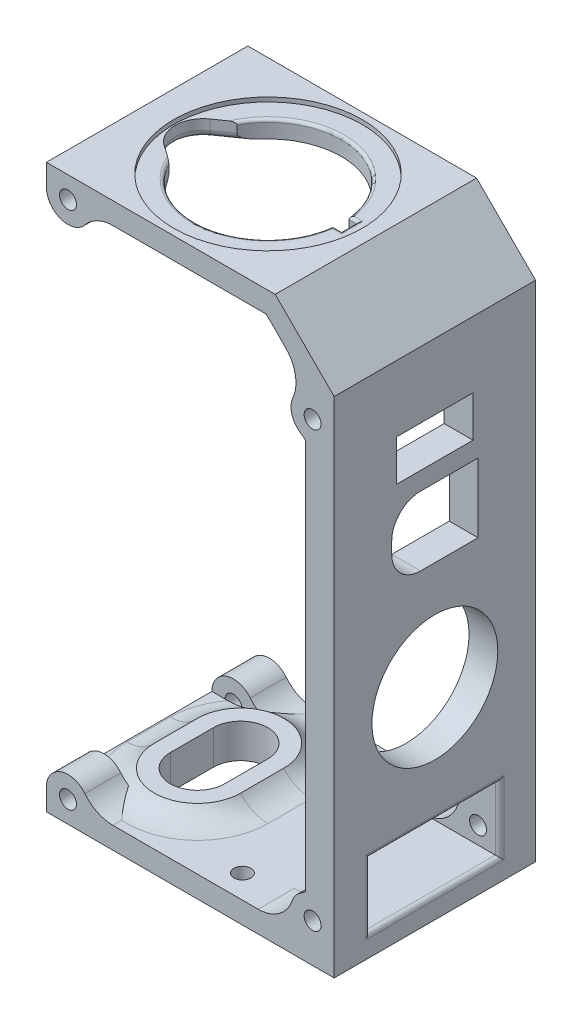
SolidWorks part; units mm, degrees
ref_plane "Front Plane" through (0, 0, 0) normal (0, 0, 1) x (1, 0, 0)
ref_plane "Top Plane" through (0, 0, 0) normal (0, 1, 0) x (1, 0, 0)
ref_plane "Right Plane" through (0, 0, 0) normal (1, 0, 0) x (0, 0, -1)
sketch "Sketch1" plane through (0, 0, 0) normal (0, 0, 1) x (1, 0, 0)
  line L0 (31.8, 78.2) -> (40, 70)
  line L1 (0, 0) -> (40, 0)
  line L3 (0, 78.2) -> (31.8, 78.2)
  line L4 (40, 0) -> (40, 70)
  line L5 (0, 0) -> (0, 3)
  line L6 (6, 75.2) -> (30.5574, 75.2)
  line L7 (35.2, 3) -> (6, 3)
  line L8 (37, 8.4) -> (37, 62.7574)
  line L10 (-74.4457, 75.2) -> (30.5574, 75.2) construction
  line L11 (1.2019, 3) -> (-74.4457, 75.2) construction
  line L12 (30.5574, 75.2) -> (37, 68.7574)
  line L13 (30.5574, 75.2) -> (37, 68.7574) construction
  line L14 (1.2019, 3) -> (37, 3) construction
  line L15 (37, 3) -> (37, 68.7574) construction
  line L16 (0, 78.2) -> (0, 75.2)
  line L17 (-81.934, 78.2) -> (31.8, 78.2) construction
  line L18 (40, 0) -> (40, 70) construction
  line L19 (0, 0) -> (-81.934, 78.2) construction
  arc A0 (37, 68.7574) -> (37, 62.7574) centre (37, 65.7574) ccw
  circle A1 centre (37, 65.7574) radius 1.175
  arc A2 (37, 8.4) -> (35.2, 3) centre (37, 5.4) ccw
  circle A3 centre (37, 5.4) radius 1.175
  arc A4 (6, 3) -> (0, 3) centre (3, 3) ccw
  circle A5 centre (3, 3) radius 1.175
  arc A6 (0, 75.2) -> (6, 75.2) centre (3, 75.2) ccw
  circle A7 centre (3, 75.2) radius 1.175
  dimension "D6" = 6
  dimension "D7" = 2.35
  dimension "D1" = 40
  dimension "D2" = 135
  dimension "D3" = 3
  dimension "D4" = 70
  dimension "D5" = 3
extrude "Boss-Extrude1" add sketch "Sketch1" along normal blind 28
sketch "Sketch2" plane through (0, 78.2, 0) normal (0, 1, 0) x (1, 0, 0)
  line L0 (31.8, -14) -> (-12.3888, -14) construction
  line L1 (31.8, -28) -> (31.8, 0) construction
  circle A0 centre (16.8, -14) radius 13.1
  dimension "D1" = 26.2
  dimension "D2" = 15
extrude "Cut-Extrude1" cut sketch "Sketch2" against normal blind 0.6
sketch "Sketch22" plane through (37, 0, 0) normal (-1, 0, 0) x (0, 0, 1)
  line L1 (0, 62.7574) -> (28, 62.7574)
  line L2 (0, 62.7574) -> (0, 8.4)
  line L3 (0, 8.4) -> (28, 8.4)
  line L4 (28, 62.7574) -> (28, 8.4)
extrude "Boss-Extrude5" add sketch "Sketch22" along normal blind 1
sketch "Sketch3" plane through (0, 77.6, 0) normal (0, 1, 0) x (1, 0, 0)
  line L0 (16.8, -14) -> (48.7255, -14) construction
  line L2 (26.9405, -12.9) -> (28.1405, -12.9)
  line L4 (26.9405, -15.1) -> (28.1405, -15.1)
  line L5 (28.1405, -12.9) -> (28.1405, -15.1)
  arc A0 (26.9405, -12.9) -> (26.9405, -15.1) centre (16.8, -14) ccw
  dimension "D1" = 20.4
  dimension "D2" = 1.2
  dimension "D3" = 2.2
extrude "Cut-Extrude2" cut sketch "Sketch3" against normal up to next
fillet "Fillet1" radius 0.4 4 edges at (6.6, 77.6, 14) (27.5405, 77.6, 15.1) (28.1405, 77.6, 14) (27.5405, 77.6, 12.9)
sketch "Sketch14" plane through (40, 0, 0) normal (1, 0, 0) x (0, 0, -1)
  line L0 (-14, 70) -> (-14, 0) construction
  line L1 (-28, 70) -> (0, 70) construction
  line L3 (-14, 28) -> (13.9962, 28) construction
  line L4 (-20, 47.8) -> (-5.2, 47.8) construction
  line L5 (-16, 52.6) -> (-8, 52.6)
  line L6 (-20, 48.6) -> (-20, 47)
  line L7 (-16, 43) -> (-8, 43)
  line L8 (-8, 52.6) -> (-8, 43)
  line L9 (-19.3, 57.95) -> (4.7334, 57.95) construction
  line L10 (-19.3, 60.8) -> (-8.7, 60.8)
  line L11 (-19.3, 60.8) -> (-19.3, 55.1)
  line L12 (-19.3, 55.1) -> (-8.7, 55.1)
  line L13 (-8.7, 60.8) -> (-8.7, 55.1)
  line L14 (-7.475, 47.8) -> (3.0305, 47.8) construction
  line L15 (-28, 0) -> (0, 0) construction
  line L17 (-23, 12) -> (-5, 12)
  line L18 (-23, 12) -> (-23, 3)
  line L19 (-23, 3) -> (-5, 3)
  line L20 (-5, 12) -> (-5, 3)
  circle A0 centre (-14, 28) radius 8.75
  circle A1 centre (-14, 16.9) radius 1.175
  circle A2 centre (-14, 39.1) radius 1.175
  circle A3 centre (-6.3, 47.8) radius 1.175
  circle A4 centre (-21.7, 47.8) radius 1.175
  arc A5 (-16, 52.6) -> (-20, 48.6) centre (-16, 48.6) ccw
  arc A6 (-20, 47) -> (-16, 43) centre (-16, 47) ccw
  circle A7 centre (-23.15, 57.95) radius 1.175
  circle A8 centre (-4.85, 57.95) radius 1.175
  point P27 (-20, 52.6)
  point P40 (-20, 43)
  dimension "D1" = 17.5
  dimension "D2" = 2.35
  dimension "D7" = 2.35
  dimension "D9" = 4
  dimension "D13" = 2.35
  dimension "D3" = 22.2
  dimension "D4" = 28
  dimension "D5" = 9.6
  dimension "D6" = 12
  dimension "D8" = 15.4
  dimension "D10" = 15
  dimension "D11" = 10.6
  dimension "D12" = 5.7
  dimension "D14" = 18.3
  dimension "D15" = 2.5
  dimension "D16" = 18
  dimension "D17" = 3
  dimension "D18" = 9
extrude "Cut-Extrude9" cut sketch "Sketch14" against normal through all
fillet "Fillet2" radius 5 6 edges at (35.2, 3, 25.5) (35.2, 3, 2.5) (37, 68.7574, 14) (6, 3, 25.5) (6, 3, 2.5) (6, 75.2, 14)
ref_plane "Plane1" through (0, 0, 14) normal (0, 0, 1) x (1, 0, 0)
sketch "Sketch16" plane through (0, 0, 14) normal (0, 0, 1) x (1, 0, 0)
  line L0 (1.825, 3) -> (4.175, 3)
  arc A0 (1.825, 3) -> (4.175, 3) centre (3, 3) ccw
  circle A1 centre (3, 3) radius 1.175 construction
extrude "Boss-Extrude2" add sketch "Sketch16" along normal mid plane 18
sketch "Sketch17" plane through (0, 3, 0) normal (0, 1, 0) x (1, 0, 0)
  line L0 (-22, -14) -> (22, -14) construction
  line L2 (10, -17) -> (10, -11) construction
  line L3 (4, -17) -> (4, -11)
  line L4 (16, -17) -> (16, -11)
  line L5 (-1.8935, -14) -> (39.7453, -14) construction
  arc A1 (4, -17) -> (16, -17) centre (10, -17) ccw
  arc A2 (16, -11) -> (4, -11) centre (10, -11) ccw
  point P8 (10, -14)
  dimension "D3" = 6
  dimension "D4" = 6
extrude "Boss-Extrude3" add sketch "Sketch17" along normal blind 1.76
sketch "Sketch18" plane through (0, 4.76, 0) normal (0, 1, 0) x (1, 0, 0)
  line L0 (-1.8826, -14) -> (40.0349, -14) construction
  line L1 (-22, -14) -> (22, -14) construction
  line L2 (10, -17) -> (10, -11) construction
  line L3 (6.23, -17) -> (6.23, -11)
  line L4 (13.77, -17) -> (13.77, -11)
  arc A1 (6.23, -17) -> (13.77, -17) centre (10, -17) ccw
  arc A2 (13.77, -11) -> (6.23, -11) centre (10, -11) ccw
  point P9 (10, -14)
  dimension "D2" = 3.77
  dimension "D3" = 6
extrude "Cut-Extrude10" cut sketch "Sketch18" against normal up to next
fillet "Fillet3" radius 5 4 edges at (4, 3, 14) (10, 3, 5) (16, 3, 14) (10, 3, 23)
sketch "Sketch19" plane through (0, 3, 0) normal (0, 1, 0) x (1, 0, 0)
  line L0 (-1.4647, -14) -> (47.0035, -14) construction
  line L1 (-22, -14) -> (22, -14) construction
  line L2 (29.4343, 0) -> (9.245, 0) construction
  line L3 (40, -22.75) -> (40, -5.25) construction
  line L4 (29.4343, -5) -> (29.4343, 0) construction
  circle A0 centre (24, -3.25) radius 1.175
  circle A1 centre (24, -24.75) radius 1.175
  dimension "D1" = 2.35
  dimension "D3" = 3.25
  dimension "D4" = 16
  dimension "D5" = 5.4343
  dimension "D2" = 21.5
extrude "Cut-Extrude11" cut sketch "Sketch19" against normal up to next
fillet "Fillet4" radius 0.6 5 edges at (36, 12, 14) (40, 7.5, 23) (40, 3, 14) (40, 7.5, 5) (40, 12, 14)
sketch "Sketch20" plane through (0, 0, 0) normal (-1, 0, 0) x (0, 0, 1)
  line L0 (14, 87.38) -> (14, -6.6146) construction
  line L1 (14, -22) -> (14, 22) construction
  line L2 (5, 3) -> (5, 109.2462) construction
  line L3 (23, 3) -> (23, 109.2462) construction
  line L4 (28, 75.2) -> (0, 75.2) construction
  line L5 (23, 75.2) -> (5, 75.2)
  line L6 (23, 75.2) -> (23, 72.2)
  line L7 (23, 72.2) -> (5, 72.2)
  line L8 (5, 75.2) -> (5, 72.2)
  line L9 (0, 72.2) -> (28, 72.2) construction
extrude "Cut-Extrude12" cut sketch "Sketch20" against normal up to next
sketch "Sketch21" plane through (0, 0, 14) normal (0, 0, 1) x (1, 0, 0)
  line L0 (1.825, 75.2) -> (4.175, 75.2)
  arc A0 (4.175, 75.2) -> (1.825, 75.2) centre (3, 75.2) ccw
extrude "Boss-Extrude4" add sketch "Sketch21" along normal mid plane 18
fillet "Fillet6" radius 3 3 edges at (37, 8.4, 2.5) (37, 8.4, 25.5) (37, 62.7574, 14)
sketch "Sketch23" plane through (40, 0, 0) normal (1, 0, 0) x (0, 0, -1)
  circle A0 centre (-23.15, 57.95) radius 1.45
  circle A1 centre (-4.85, 57.95) radius 1.45
  circle A2 centre (-21.7, 47.8) radius 1.45
  circle A3 centre (-6.3, 47.8) radius 1.45
  circle A4 centre (-14, 39.1) radius 1.6
  circle A5 centre (-14, 16.9) radius 1.6
extrude "Boss-Extrude6" add sketch "Sketch23" against normal blind 1
sketch "Sketch24" plane through (0, 78.2, 0) normal (0, 1, 0) x (1, 0, 0)
  line L0 (10.8, -20.8616) -> (10.8, -7.1384)
  line L4 (10.8, -7.1384) -> (5.5631, -10.8053)
  line L5 (5.5631, -17.1947) -> (10.8, -20.8616)
  line L8 (0, -28) -> (0, 0) construction
  line L9 (0, -14) -> (-6.2983, -14) construction
  line L10 (-22, -14) -> (22, -14) construction
  arc A0 (5.5631, -17.1947) -> (5.5631, -10.8053) centre (7.8, -14) cw
  point P11 (1.0006, -14)
  dimension "D1" = 3.9
  dimension "D4" = 3
  dimension "D2" = 10.8
  dimension "D3" = 55
extrude "Cut-Extrude13" cut sketch "Sketch24" against normal up to next
fillet "Fillet7" radius 1 3 edges at (6.6652, 75.2, 17.9664) (6.6652, 75.2, 10.0336) (3.9, 75.2, 14)
